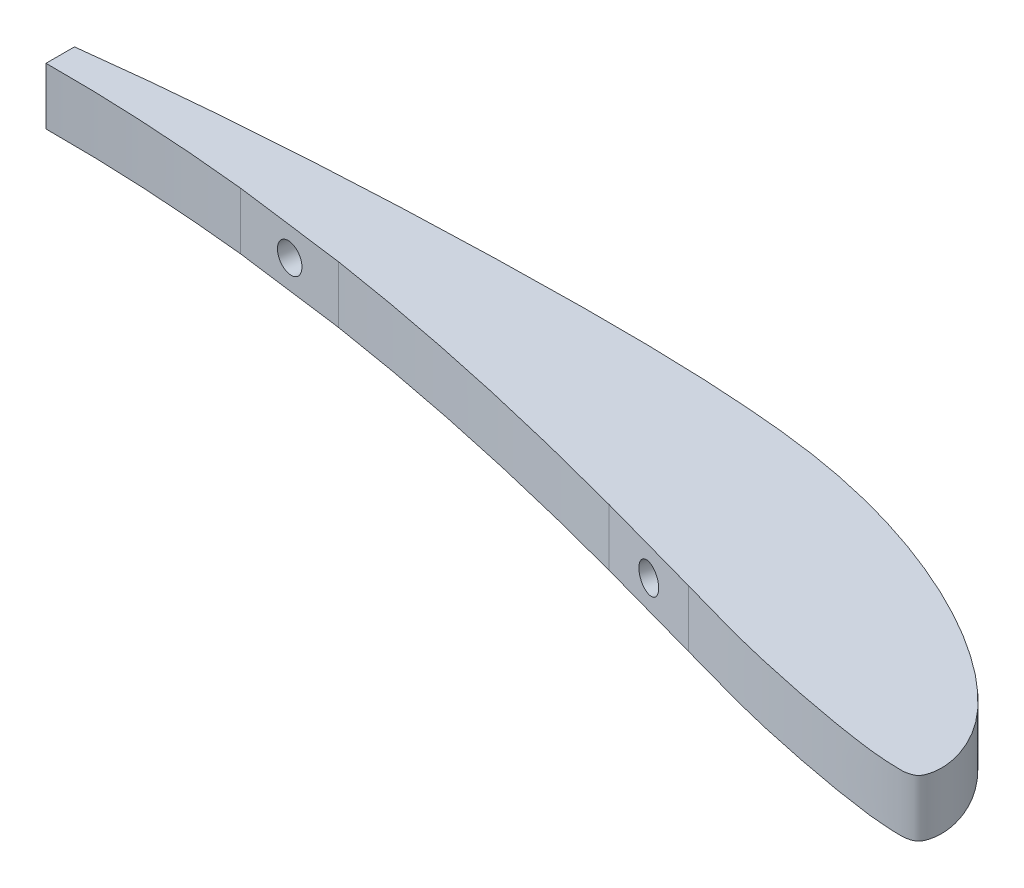
SolidWorks part; units mm, degrees
material "6061-T6 (SS)"
ref_plane "Front Plane" through (0, 0, 0) normal (0, 0, 1) x (1, 0, 0)
ref_plane "Top Plane" through (0, 0, 0) normal (0, 1, 0) x (1, 0, 0)
ref_plane "Right Plane" through (0, 0, 0) normal (1, 0, 0) x (0, 0, -1)
sketch "Sketch1" plane through (0, 0, 0) normal (0, 1, 0) x (1, 0, 0)
  line L0 (-573.3037, -923.603) -> (-597.7764, -916.8025)
  line L1 (-674.9037, -900.056) -> (-700.0885, -896.757)
  line L2 (-808.6993, -905.2883) -> (-509.8037, -905.2883) construction
  line L3 (-509.8037, -872.3949) -> (-509.8037, -983.6564) construction
  line L6 (-745.9648, -894.3289) -> (-745.9648, -887.9789)
  spline S0 degree 3 poles (-808.6993, -905.2883) (-808.6982, -905.2962) (-807.4752, -904.613) (-806.127, -903.9501) (-802.619, -902.2394) (-797.9088, -900.4691) (-791.3652, -898.6563) (-783.4284, -897.1151) (-774.1889, -895.8336) (-763.8228, -894.9001) (-752.4549, -894.3653) (-740.2355, -894.2603) (-727.3126, -894.6171) (-713.8417, -895.4321) (-699.9775, -896.7002) (-685.8744, -898.4039) (-671.6834, -900.5041) (-657.5508, -902.9538) (-643.6166, -905.7091) (-630.0078, -908.6898) (-616.8435, -911.8333) (-604.2325, -915.0568) (-592.2678, -918.2813) (-581.0316, -921.4177) (-570.588, -924.3709) (-560.9843, -927.0851) (-552.1531, -929.3518) (-544.047, -931.1293) (-536.6863, -932.606) (-530.1089, -933.7965) (-524.3814, -934.6811) (-519.5727, -935.3098) (-515.7227, -935.5093) (-512.9049, -935.6145) (-510.7315, -934.8036) (-509.9959, -932.8526) (-509.7106, -930.6803) (-509.9795, -928.0591) (-510.7719, -925.1755) (-512.1317, -922.0927) (-514.0562, -918.8779) (-516.6421, -915.6169) (-519.8781, -912.3368) (-523.7109, -909.0096) (-528.1441, -905.6984) (-533.1518, -902.4451) (-538.7081, -899.284) (-544.7994, -896.2706) (-551.3874, -893.4216) (-558.448, -890.7922) (-565.9536, -888.4206) (-573.9046, -886.402) (-582.3026, -884.7325) (-591.1896, -883.4954) (-600.566, -882.6533) (-610.3988, -882.0314) (-620.642, -881.6827) (-631.2334, -881.5506) (-642.1094, -881.5982) (-653.1892, -881.7765) (-664.3815, -882.0722) (-675.5918, -882.4614) (-686.7321, -882.9614) (-697.7225, -883.5745) (-708.4921, -884.2944) (-718.9726, -885.1304) (-729.1025, -886.0651) (-738.8188, -887.1017) (-748.0636, -888.2218) (-756.7807, -889.4205) (-764.9179, -890.6901) (-772.4286, -892.0204) (-779.2704, -893.3968) (-785.4053, -894.8135) (-790.8008, -896.2561) (-795.4314, -897.7136) (-799.288, -899.1607) (-802.4245, -900.7274) (-804.759, -902.3492) (-806.7523, -903.8913) (-807.6542, -904.6341) (-808.7005, -905.2805) (-808.6993, -905.2883) (-808.6982, -905.2962) (-807.4752, -904.613) knots -0.00098 0 0 0 0.001 0.004147 0.009748 0.018044 0.028864 0.041831 0.056714 0.073341 0.091508 0.111022 0.131662 0.153208 0.175433 0.19811 0.221011 0.243906 0.266573 0.28881 0.310405 0.331178 0.350944 0.369556 0.386865 0.402753 0.417196 0.43038 0.442363 0.453032 0.462284 0.470026 0.476177 0.48065 0.483553 0.486421 0.489953 0.494097 0.498851 0.504197 0.510125 0.516691 0.524012 0.532092 0.540898 0.550403 0.560581 0.571396 0.582828 0.59483 0.607347 0.620384 0.633969 0.6482 0.663194 0.678899 0.695227 0.712113 0.729459 0.747143 0.76501 0.782905 0.800688 0.818242 0.835449 0.852212 0.86843 0.884009 0.898855 0.912882 0.926011 0.938167 0.94929 0.959322 0.968217 0.975948 0.982474 0.987905 0.992517 0.996351 0.99902 1 1 1 1.001 1.004147 1.009748 only from (-808.6993, -905.2883) to (-808.6993, -905.2883) construction
  spline S1 degree 3 poles (-808.6993, -905.2883) (-808.6982, -905.2962) (-807.4752, -904.613) (-806.127, -903.9501) (-802.619, -902.2394) (-797.9088, -900.4691) (-791.3652, -898.6563) (-783.4284, -897.1151) (-774.1889, -895.8336) (-763.8228, -894.9001) (-752.4549, -894.3653) (-740.2355, -894.2603) (-727.3126, -894.6171) (-713.8417, -895.4321) (-699.9775, -896.7002) (-685.8744, -898.4039) (-671.6834, -900.5041) (-657.5508, -902.9538) (-643.6166, -905.7091) (-630.0078, -908.6898) (-616.8435, -911.8333) (-604.2325, -915.0568) (-592.2678, -918.2813) (-581.0316, -921.4177) (-570.588, -924.3709) (-560.9843, -927.0851) (-552.1531, -929.3518) (-544.047, -931.1293) (-536.6863, -932.606) (-530.1089, -933.7965) (-524.3814, -934.6811) (-519.5727, -935.3098) (-515.7227, -935.5093) (-512.9049, -935.6145) (-510.7315, -934.8036) (-509.9959, -932.8526) (-509.7106, -930.6803) (-509.9795, -928.0591) (-510.7719, -925.1755) (-512.1317, -922.0927) (-514.0562, -918.8779) (-516.6421, -915.6169) (-519.8781, -912.3368) (-523.7109, -909.0096) (-528.1441, -905.6984) (-533.1518, -902.4451) (-538.7081, -899.284) (-544.7994, -896.2706) (-551.3874, -893.4216) (-558.448, -890.7922) (-565.9536, -888.4206) (-573.9046, -886.402) (-582.3026, -884.7325) (-591.1896, -883.4954) (-600.566, -882.6533) (-610.3988, -882.0314) (-620.642, -881.6827) (-631.2334, -881.5506) (-642.1094, -881.5982) (-653.1892, -881.7765) (-664.3815, -882.0722) (-675.5918, -882.4614) (-686.7321, -882.9614) (-697.7225, -883.5745) (-708.4921, -884.2944) (-718.9726, -885.1304) (-729.1025, -886.0651) (-738.8188, -887.1017) (-748.0636, -888.2218) (-756.7807, -889.4205) (-764.9179, -890.6901) (-772.4286, -892.0204) (-779.2704, -893.3968) (-785.4053, -894.8135) (-790.8008, -896.2561) (-795.4314, -897.7136) (-799.288, -899.1607) (-802.4245, -900.7274) (-804.759, -902.3492) (-806.7523, -903.8913) (-807.6542, -904.6341) (-808.7005, -905.2805) (-808.6993, -905.2883) (-808.6982, -905.2962) (-807.4752, -904.613) knots -0.00098 0 0 0 0.001 0.004147 0.009748 0.018044 0.028864 0.041831 0.056714 0.073341 0.091508 0.111022 0.131662 0.153208 0.175433 0.19811 0.221011 0.243906 0.266573 0.28881 0.310405 0.331178 0.350944 0.369556 0.386865 0.402753 0.417196 0.43038 0.442363 0.453032 0.462284 0.470026 0.476177 0.48065 0.483553 0.486421 0.489953 0.494097 0.498851 0.504197 0.510125 0.516691 0.524012 0.532092 0.540898 0.550403 0.560581 0.571396 0.582828 0.59483 0.607347 0.620384 0.633969 0.6482 0.663194 0.678899 0.695227 0.712113 0.729459 0.747143 0.76501 0.782905 0.800688 0.818242 0.835449 0.852212 0.86843 0.884009 0.898855 0.912882 0.926011 0.938167 0.94929 0.959322 0.968217 0.975948 0.982474 0.987905 0.992517 0.996351 0.99902 1 1 1 1.001 1.004147 1.009748 only from (-808.6993, -905.2883) to (-808.6993, -905.2883)
  dimension "D1" = 25.4
  dimension "D2" = 63.5
  dimension "D3" = 25.4
  dimension "D4" = 165.1
  dimension "D9" = 6.35
extrude "Boss-Extrude1" add sketch "Sketch1" along normal mid plane 12.7 contours L6 S1 | S1 L0 | S1 L1 region at (-586.2796, 0, 919.9807) region at (-604.7361, 0, 901.087) region at (-687.557, 0, 898.337)
hole_wizard "1/4 (0.25) Diameter Hole1" positions "3DSketch2" profile "Sketch4" hole size "1/4" standard "ANSI Inch"
sketch3d "3DSketch2"
  line L0 (-573.3037, 6.35, 923.603) -> (-573.3037, -6.35, 923.603) construction
  line L1 (-573.3037, 6.35, 923.603) -> (-597.7764, 6.35, 916.8025) construction
  line L2 (-700.0885, 6.35, 896.757) -> (-700.0885, -6.35, 896.757) construction
  line L3 (-674.9037, 6.35, 900.056) -> (-700.0885, 6.35, 896.757) construction
  point P0 (-585.54, 0, 920.2028)
  point P2 (-687.4961, 0, 898.4065)
  dimension "D1" = 12.7
  dimension "D2" = 6.35
  dimension "D3" = 12.7
  dimension "D4" = 6.35
sketch "Sketch4" plane through (-585.54, 0, 920.2028) normal (0, 1, 0) x (0.9635, 0, 0.2677)
  line L0 (0, 0) -> (0, 14.6077)
  line L1 (0, 14.6077) -> (3.175, 12.7)
  line L2 (3.175, 12.7) -> (3.175, 0)
  line L5 (3.175, 0) -> (0, 0)
  line L10 (0, 14.6077) -> (-3.175, 12.7) construction
  line L11 (0, -6.35) -> (0, 107.95) construction
  dimension "Hole Dia." = 6.35
  dimension "Hole Depth" = 12.7
  dimension "Drill Angle" = 118
